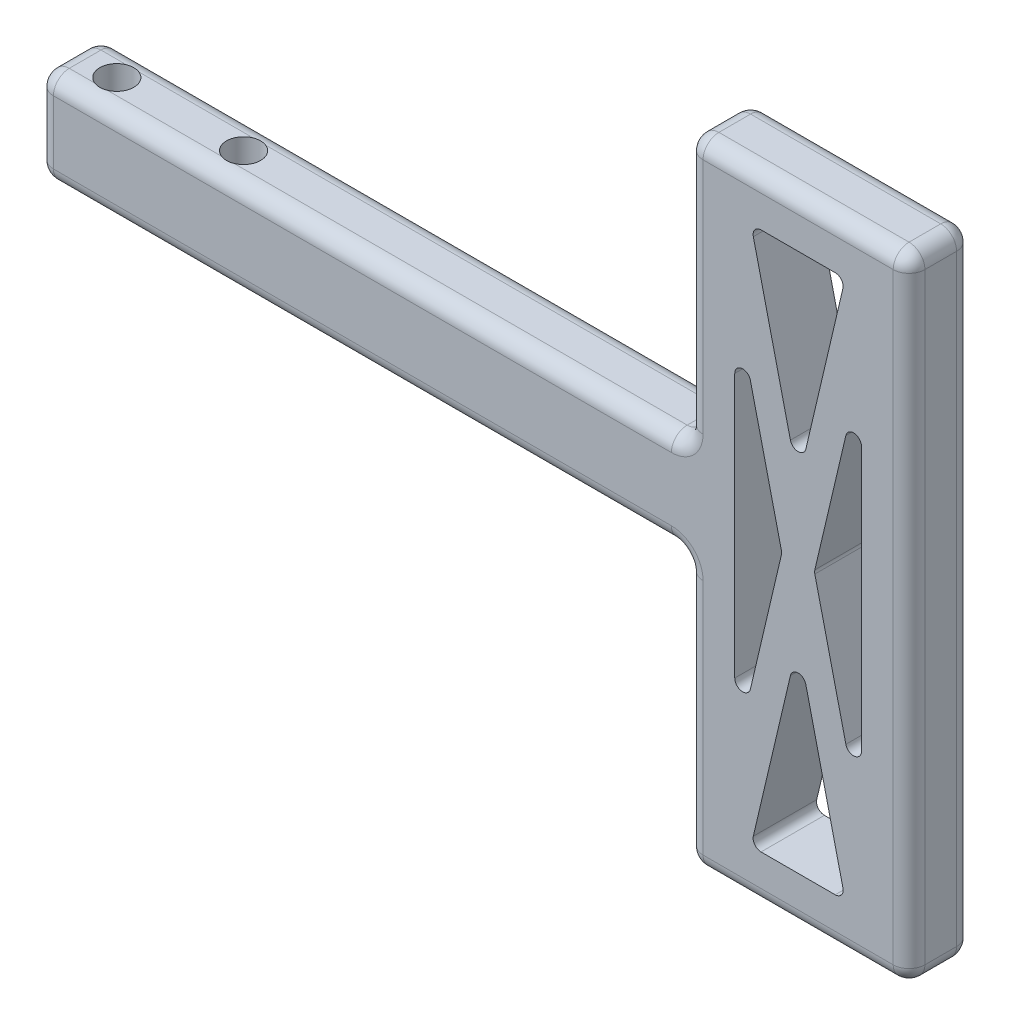
SolidWorks part; units mm, degrees
ref_plane "Front Plane" through (0, 0, 0) normal (0, 0, 1) x (1, 0, 0)
ref_plane "Top Plane" through (0, 0, 0) normal (0, 1, 0) x (1, 0, 0)
ref_plane "Right Plane" through (0, 0, 0) normal (1, 0, 0) x (0, 0, -1)
sketch "Sketch1" plane through (0, 0, 0) normal (0, 0, 1) x (1, 0, 0)
  line L0 (0, 0) -> (96, 0) construction
  line L1 (76, -6) -> (76, -40)
  line L2 (-6, 6) -> (76, 6)
  line L3 (-6, 6) -> (-6, -6)
  line L4 (-6, -6) -> (76, -6)
  line L6 (35, -6) -> (35, 6) construction
  line L7 (-6, 0) -> (104, 0) construction
  line L12 (82, -6) -> (82, -34) construction
  line L13 (82, -34) -> (98, -34) construction
  line L14 (76, 40) -> (104, 40)
  line L15 (76, 40) -> (76, 6)
  line L16 (76, -40) -> (104, -40)
  line L17 (104, 40) -> (104, -40)
  line L18 (90, -40) -> (90, 40) construction
  line L19 (76, 0) -> (104, 0) construction
  line L20 (98, 34) -> (98, -34) construction
  line L21 (82, 34) -> (98, 34) construction
  line L22 (82, 34) -> (82, 6) construction
  line L23 (82, 6) -> (82, -6) construction
  line L24 (98, 34) -> (-11353.9667, -48636.8584) construction
  line L25 (82, 34) -> (11533.9667, -48636.8584) construction
  line L26 (80.0532, 33.5419) -> (11532.0199, -48637.3165) construction
  line L27 (96.0532, 34.4581) -> (-11355.9135, -48636.4003) construction
  line L28 (83.9468, 34.4581) -> (11535.9135, -48636.4003) construction
  line L29 (99.9468, 33.5419) -> (-11352.0199, -48637.3165) construction
  line L30 (84.0546, 34) -> (90, 8.7321)
  line L31 (90, 8.7321) -> (95.9454, 34)
  line L32 (95.9454, 34) -> (84.0546, 34)
  line L33 (82, 25.2679) -> (82, -25.2679)
  line L34 (82, -25.2679) -> (87.9454, 0)
  line L35 (87.9454, 0) -> (82, 25.2679)
  line L36 (98, 25.2679) -> (92.0546, 0)
  line L37 (92.0546, 0) -> (98, -25.2679)
  line L38 (98, -25.2679) -> (98, 25.2679)
  line L39 (84.0546, -34) -> (95.9454, -34)
  line L40 (95.9454, -34) -> (90, -8.7321)
  line L41 (90, -8.7321) -> (84.0546, -34)
  circle A0 centre (0, 0) radius 2.1 construction
  circle A1 centre (96, 0) radius 2.1 construction
  circle A2 centre (80, 0) radius 2.1 construction
  point P201 (35, 0)
  point P251 (90, 0)
  dimension "D1" = 4.2
  dimension "D2" = 4.2
  dimension "D6" = 4.2
  dimension "8*12" = 96
  dimension "D3" = 6
  dimension "D4" = 8
  dimension "D5" = 6
  dimension "16" = 16
  dimension "D7" = 4
  dimension "D8" = 28
  dimension "D9" = 80
  dimension "D10" = 6
  dimension "D11" = 2
  dimension "D12" = 2
extrude "Boss-Extrude1" add sketch "Sketch1" along normal blind 8
sketch "Sketch2" plane through (0, -6, 0) normal (0, -1, 0) x (1, 0, 0)
  line L0 (-6, 8) -> (-6, 0) construction
  circle A0 centre (0, 4) radius 2.15
  circle A1 centre (16, 4) radius 2.15
  dimension "D1" = 4.3
  dimension "D2" = 4.3
  dimension "D3" = 16
  dimension "D4" = 6
extrude "Cut-Extrude1" cut sketch "Sketch2" against normal blind 18
fillet "Fillet1" radius 2 24 edges at (76, -23, 0) (76, 23, 8) (76, 23, 0) (104, 0, 0) (104, 0, 8) (90, 40, 0) (90, 40, 8) (90, -40, 0) (90, -40, 8) (35, -6, 0) (76, -23, 8) (35, -6, 8) (35, 6, 8) (35, 6, 0) (104, 40, 4) (104, -40, 4) (76, -40, 4) (-6, -6, 4) (76, -6, 4) (76, 6, 4) (-6, 6, 4) (76, 40, 4) (-6, 0, 0) (-6, 0, 8)
fillet "Fillet2" radius 1 12 edges at (98, 25.2679, 4) (84.0546, -34, 4) (95.9454, -34, 4) (98, -25.2679, 4) (92.0546, 0, 4) (90, -8.7321, 4) (82, -25.2679, 4) (87.9454, 0, 4) (82, 25.2679, 4) (90, 8.7321, 4) (95.9454, 34, 4) (84.0546, 34, 4)
